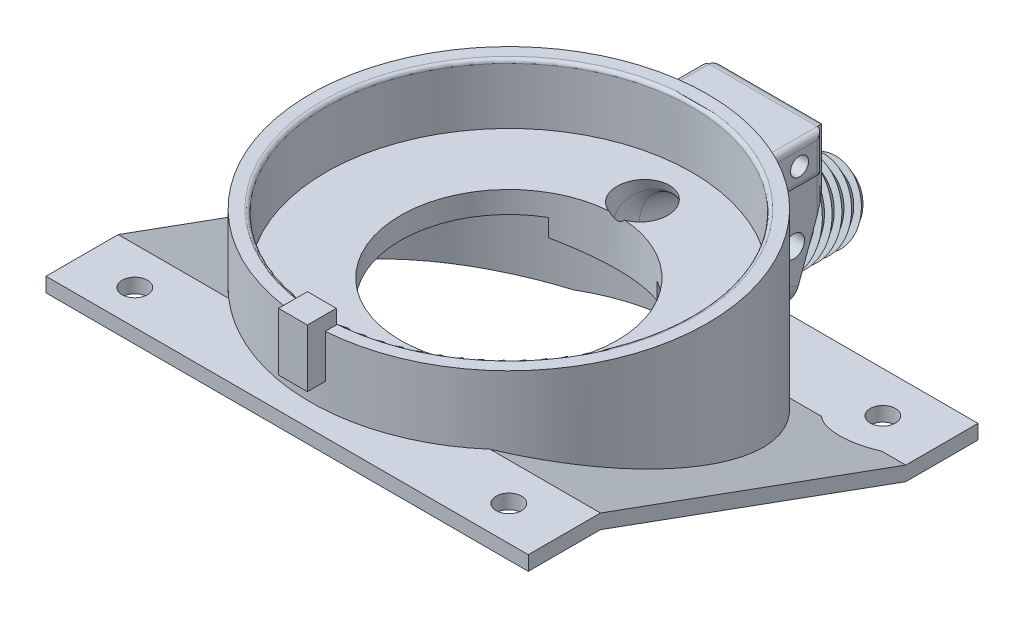
SolidWorks part; units mm, degrees
ref_plane "Front Plane" through (0, 0, 0) normal (0, 0, 1) x (1, 0, 0)
ref_plane "Top Plane" through (0, 0, 0) normal (0, 1, 0) x (1, 0, 0)
ref_plane "Right Plane" through (0, 0, 0) normal (1, 0, 0) x (0, 0, -1)
sketch "Sketch1" plane through (0, 0, 0) normal (0, 1, 0) x (1, 0, 0)
  line L0 (0, -33.8208) -> (0, 34.4324) construction
  line L1 (-28.4, 28.4) -> (28.4, 28.4)
  line L2 (-28.4, 28.4) -> (-28.4, -28.4)
  line L3 (-28.4, -28.4) -> (28.4, -28.4)
  line L4 (28.4, 28.4) -> (28.4, -28.4)
  line L5 (-28.4, 28.4) -> (28.4, -28.4) construction
  line L6 (-28.4, -28.4) -> (28.4, 28.4) construction
  line L7 (-31.5183, 0) -> (32.8915, 0) construction
  circle A0 centre (0, 0) radius 19.175
  point P0 (0, 0)
  dimension "D3" = 38.35
  dimension "D1" = 56.8
  dimension "D2" = 56.8
extrude "Boss-Extrude1" add sketch "Sketch1" along normal blind 5 contours L2 L3 L4 L1
extrude "Cut-Extrude1" cut sketch "Sketch1<4>" along normal blind 1.65 contours A0
sketch "Sketch1<4>" plane through (0, 0, 0) normal (0, 1, 0) x (1, 0, 0) same geometry as "Sketch1"
sketch "Sketch3" plane through (0, 5, 0) normal (0, 1, 0) x (1, 0, 0)
  circle A0 centre (0, 0) radius 15
  circle A1 centre (0, 0) radius 27.5
  dimension "D1" = 30
  dimension "D2" = 55
extrude "Cut-Extrude2" cut sketch "Sketch3" against normal up to surface (3.35 mm away) contours A0 up to face at (0, 1.65, 19.175)
extrude "Boss-Extrude2" add sketch "Sketch3<3>" along normal blind 25.04
sketch "Sketch3<3>" plane through (0, 5, 0) normal (0, 1, 0) x (1, 0, 0) same geometry as "Sketch3"
sketch "Sketch4" plane through (0, 30.04, 0) normal (0, 1, 0) x (1, 0, 0)
  circle A0 centre (0, 0) radius 27.5 construction
  circle A1 centre (0, 0) radius 27.5
  circle A2 centre (0, 0) radius 25.35
  dimension "D1" = 50.7
extrude "Boss-Extrude3" add sketch "Sketch4" along normal blind 8.3
sketch "Sketch14" plane through (0, 0, 28.4) normal (0, 0, 1) x (1, 0, 0)
  line L0 (27.5, 38.34) -> (-27.5, 38.34) construction
  line L1 (-2, 32.34) -> (2, 32.34)
  line L2 (-2, 32.34) -> (-2, 40.34)
  line L3 (-2, 40.34) -> (2, 40.34)
  line L4 (2, 32.34) -> (2, 40.34)
  line L5 (-2, 32.34) -> (2, 40.34) construction
  line L6 (-2, 40.34) -> (2, 32.34) construction
  line L8 (0, -5.1495) -> (0, 66.3845) construction
  point P0 (0, 36.34)
  dimension "D1" = 8
  dimension "D2" = 2
  dimension "D3" = 4
extrude "Boss-Extrude9" add sketch "Sketch14" against normal blind 2.5 and the other way blind 1.5
fillet "Fillet3" radius 0.5 1 edges at (0, 38.34, 25.35)
sketch "Sketch15" plane through (0, 0, 0) normal (1, 0, 0) x (0, 0, -1)
  line L0 (19.3563, 27.6919) -> (17.7409, 32.1304)
  line L1 (21.747, 25.3013) -> (58.7764, 11.8237)
  line L4 (27.5, 5) -> (27.5, 38.34) construction
  line L5 (25.35, 30.04) -> (-25.35, 30.04) construction
  arc A0 (19.3563, 27.6919) -> (21.747, 25.3013) centre (23.1151, 29.06) ccw
  dimension "D3" = 4
  dimension "D1" = 70
  dimension "D2" = 70
ref_plane "Plane2" through (0, 32.1304, -17.7409) normal (0, -0.9397, -0.342) x (-1, 0, 0)
sketch "Sketch16" plane through (0, 32.1304, -17.7409) normal (0, -0.9397, -0.342) x (-1, 0, 0)
  circle A0 centre (0, 0) radius 3.5
  dimension "D1" = 7
ref_axis "Axis2" through (0, 35.371, 5.9193) along (0, -0.342, -0.9397)
ref_plane "Plane5" through (0, -8.5427, -23.4709) normal (0, -0.342, -0.9397) x (1, 0, 0)
sketch "Sketch20" plane through (0, -8.5427, -23.4709) normal (0, -0.342, -0.9397) x (1, 0, 0)
  line L1 (-7.5, -38.7133) -> (7.5, -38.7133)
  line L2 (-7.5, -38.7133) -> (-7.5, -23.7133)
  line L3 (-7.5, -23.7133) -> (7.5, -23.7133)
  line L4 (7.5, -38.7133) -> (7.5, -23.7133)
  line L5 (-7.5, -38.7133) -> (7.5, -23.7133) construction
  line L6 (-7.5, -23.7133) -> (7.5, -38.7133) construction
  point P0 (0, -31.2133)
  dimension "D1" = 15
  dimension "D2" = 15
extrude "Boss-Extrude11" add sketch "Sketch20" against normal up to surface (10.9122 mm away) up to face at (0, 5, -27.5)
fillet "Fillet6" radius 3 1 edges at (-7.5, 14.673, -29.0194)
fillet "Fillet7" radius 3 1 edges at (7.5, 14.673, -29.0194)
sketch "Sketch22" plane through (0, -8.5427, -23.4709) normal (0, -0.342, -0.9397) x (1, 0, 0)
  line L0 (0, -31.2133) -> (-8.9055, -31.2133) construction
ref_plane "Plane6" through (0, 29.3309, -10.6756) normal (0, -0.9397, 0.342) x (-1, 0, 0)
sketch "Sketch26" plane through (0, 29.3309, -10.6756) normal (0, -0.9397, 0.342) x (-1, 0, 0)
  line L0 (0, 24.9772) -> (7.5, 24.9772)
  line L1 (0, 11.782) -> (0, 51.1878) construction
  line L3 (0, 24.9772) -> (8.9055, 24.9772) construction
  line L4 (0, 24.9772) -> (0, 50.9772)
  line L5 (7.5, 24.9772) -> (6, 26.9772)
  line L6 (6, 26.9772) -> (7, 26.9772)
  line L7 (7, 26.9772) -> (5.5, 28.9772)
  line L8 (5.5, 28.9772) -> (6.5, 28.9772)
  line L9 (6.5, 28.9772) -> (5, 30.9772)
  line L10 (5, 30.9772) -> (6, 30.9772)
  line L11 (6, 30.9772) -> (4.5, 32.9772)
  line L12 (4.5, 32.9772) -> (5.5, 32.9772)
  line L13 (5.5, 32.9772) -> (4, 34.9772)
  line L14 (4, 34.9772) -> (5, 34.9772)
  line L15 (5, 34.9772) -> (3.5, 36.9772)
  line L16 (3.5, 36.9772) -> (4.5, 36.9772)
  line L17 (4.5, 36.9772) -> (3, 38.9772)
  line L18 (3, 38.9772) -> (4, 38.9772)
  line L19 (4, 38.9772) -> (2.5, 40.9772)
  line L20 (2.5, 40.9772) -> (3.5, 40.9772)
  line L21 (3.5, 40.9772) -> (2, 42.9772)
  line L22 (2, 42.9772) -> (3, 42.9772)
  line L23 (3, 42.9772) -> (1.5, 44.9772)
  line L24 (1.5, 44.9772) -> (2.5, 44.9772)
  line L25 (2.5, 44.9772) -> (1, 46.9772)
  line L26 (1, 46.9772) -> (2, 46.9772)
  line L27 (2, 46.9772) -> (0.5, 48.9772)
  line L28 (0.5, 48.9772) -> (1.5, 48.9772)
  line L29 (1.5, 48.9772) -> (0, 50.9772)
  dimension "D1" = 7.5
  dimension "D2" = 2.5
  dimension "D3" = 1
  dimension "D4" = 2.5
  dimension "D5" = 0.5
  dimension "D6" = 2.5
  dimension "D7" = 1
  dimension "D8" = 2.5
  dimension "D9" = 1
  dimension "D10" = 0.5
  dimension "D11" = 2.5
  dimension "D12" = 1
  dimension "D13" = 2.5
  dimension "D14" = 1
  dimension "D15" = 2.5
  dimension "D16" = 1
  dimension "D17" = 2.5
  dimension "D18" = 1
  dimension "D19" = 1
  dimension "D20" = 2.5
  dimension "D21" = 1
  dimension "D22" = 0.5
  dimension "D23" = 1
  dimension "D24" = 0.5
  dimension "D25" = 2.5
  dimension "D26" = 1
  dimension "D27" = 2.5
revolve "Revolve4" add sketch "Sketch26" angle 360 about L1
sweep "Cut-Sweep3" cut profiles "Sketch16" path "Sketch15"
sketch "Sketch29" plane through (-7.5, 0, 0) normal (-1, 0, 0) x (0, 0, 1)
  line L0 (-50.9292, 14.6798) -> (29.578, 43.982) construction
  line L1 (-26.4575, 18.798) -> (-26.4575, 31.5681) construction
  line L2 (-31.9575, 34.9439) -> (-31.9575, 5.6751) construction
  circle A0 centre (-31.9575, 21.5849) radius 1.5
  circle A1 centre (-31.9575, 31.5849) radius 1.25
  dimension "D1" = 3
  dimension "D2" = 5.5
  dimension "D3" = 2.5
  dimension "D4" = 10
sketch "Sketch31" plane through (0, 38.34, 0) normal (0, 1, 0) x (1, 0, 0)
  line L0 (0, -5.9193) -> (0, 49.5105) construction
  line L1 (-7.5, 36.7116) -> (7.5, 36.7116)
  line L2 (-7.5, 36.7116) -> (-7.5, 25.6916)
  line L3 (-7.5, 25.6916) -> (7.5, 25.6916)
  line L4 (7.5, 36.7116) -> (7.5, 25.6916)
  line L5 (-7.5, 36.7116) -> (7.5, 25.6916) construction
  line L6 (-7.5, 25.6916) -> (7.5, 36.7116) construction
  line L7 (0, 36.7116) -> (7.5, 36.7116) construction
  line L8 (-7.5, 26.4575) -> (-7.5, 36.7116) construction
  point P0 (0, 31.2016)
  dimension "D1" = 0
  dimension "D2" = 0
extrude "Boss-Extrude12" add sketch "Sketch31" against normal up to surface (10.5041 mm away) up to face at (0, 29.2529, -32.8185)
sketch "Sketch33" plane through (0, 0, -36.7116) normal (0, 0, -1) x (-1, 0, 0)
  line L0 (7.5, 27.8359) -> (7.5, 38.34) construction
  line L1 (-7.5, 38.34) -> (7.5, 38.34)
  line L2 (-7.5, 38.34) -> (-7.5, 34.34)
  line L3 (-7.5, 34.34) -> (7.5, 34.34)
  line L4 (7.5, 38.34) -> (7.5, 34.34)
  dimension "D1" = 4
extrude "Cut-Extrude3" cut sketch "Sketch33" against normal up to surface (10.2541 mm away) up to face at (0, 5, -27.5)
extrude "Cut-Extrude4" cut sketch "Sketch29" against normal through all
fillet "Fillet8" radius 1.5 3 edges at (7.5, 31.088, -36.7116) (0, 34.34, -36.7116) (-7.5, 31.088, -36.7116)
ref_plane "Plane7" through (0, -12.9548, -35.5929) normal (0, 0.342, 0.9397) x (1, 0, 0)
sketch "Sketch35" plane through (0, -12.9548, -35.5929) normal (0, 0.342, 0.9397) x (1, 0, 0)
  line L1 (-9.025, 24.3636) -> (9.688, 24.3636)
  line L2 (-9.025, 24.3636) -> (-9.025, 36.9741)
  line L3 (-9.025, 36.9741) -> (9.688, 36.9741)
  line L4 (9.688, 24.3636) -> (9.688, 36.9741)
extrude "Cut-Extrude5" cut sketch "Sketch35" against normal blind 10
sketch "Sketch43" plane through (0, -12.9548, -35.5929) normal (0, 0.342, 0.9397) x (1, 0, 0)
  line L1 (10.1928, 24.0006) -> (-11.4613, 24.0006)
  line L2 (10.1928, 24.0006) -> (10.1928, 39.7537)
  line L3 (10.1928, 39.7537) -> (-11.4613, 39.7537)
  line L4 (-11.4613, 24.0006) -> (-11.4613, 39.7537)
extrude "Cut-Extrude6" cut sketch "Sketch43" along normal blind 1.4
sketch "Sketch44" plane through (0, 0, 0) normal (0, -1, 0) x (1, 0, 0)
  line L0 (-28.4, -28.4) -> (-28.4, 28.4) construction
  line L1 (28.4, -28.4) -> (-28.4, -28.4)
  line L2 (28.4, -28.4) -> (28.4, 28.4)
  line L3 (28.4, 28.4) -> (-28.4, 28.4)
  line L4 (-28.4, -28.4) -> (-28.4, 28.4)
  line L5 (-28.4, 28.4) -> (28.4, 28.4) construction
  line L6 (-28.4, -28.4) -> (28.4, -28.4) construction
extrude "Cut-Extrude8" cut sketch "Sketch44" against normal blind 13.5
sketch "Sketch48" plane through (0, 22.2832, -8.1104) normal (0, -0.9397, 0.342) x (1, 0, 0)
  line L1 (4.5, -20.2395) -> (-4.5, -20.2395)
  line L2 (4.5, -20.2395) -> (4.5, -24.9772)
  line L3 (4.5, -24.9772) -> (-4.5, -24.9772)
  line L4 (-4.5, -20.2395) -> (-4.5, -24.9772)
ref_plane "Plane3" through (-33.4, 0, 0) normal (1, 0, 0) x (0, 0, -1)
sketch "Sketch49" plane through (-33.4, 0, 0) normal (1, 0, 0) x (0, 0, -1)
  line L0 (-27.5, 13.5) -> (27.5, 13.5) construction
  line L1 (31.5813, 13.5) -> (21.5813, 13.5)
  line L2 (31.5813, 13.5) -> (31.5813, 11.5)
  line L3 (31.5813, 11.5) -> (21.5813, 11.5)
  line L4 (21.5813, 13.5) -> (-20.7049, 28.8909)
  line L5 (21.5813, 11.5) -> (-20.7049, 26.8909)
  line L9 (-20.7049, 28.8909) -> (-30.7049, 28.8909)
  line L11 (-20.7049, 26.8909) -> (-30.7049, 26.8909)
  line L12 (-30.7049, 28.8909) -> (-30.7049, 26.8909)
  dimension "D1" = 0
  dimension "D2" = 2
  dimension "D3" = 10
  dimension "D4" = 0
  dimension "D5" = 45
  dimension "D7" = 10
  dimension "D8" = 2
  dimension "D9" = 10
extrude "Boss-Extrude14" add sketch "Sketch49" along normal blind 66.8
extrude "Boss-Extrude15" add sketch "Sketch48" along normal up to surface (1.9804 mm away) up to face at (0, 13.5, -25.9011)
sketch "Sketch50" plane through (0, 17.0908, -6.2206) normal (0, -0.9397, 0.342) x (1, 0, 0)
  line L1 (-33.4, -16.3466) -> (33.4, -16.3466)
  line L2 (-33.4, -16.3466) -> (-33.4, 28.6534)
  line L3 (-33.4, 28.6534) -> (33.4, 28.6534)
  line L4 (33.4, -16.3466) -> (33.4, 28.6534)
extrude "Cut-Extrude9" cut sketch "Sketch50" along normal blind 66.8
sketch "Sketch51" plane through (0, 26.8909, 0) normal (0, -1, 0) x (1, 0, 0)
  line L1 (-33.4, 20.7049) -> (33.4, 20.7049)
  line L2 (-33.4, 20.7049) -> (-33.4, 30.7049)
  line L3 (-33.4, 30.7049) -> (33.4, 30.7049)
  line L4 (33.4, 20.7049) -> (33.4, 30.7049)
extrude "Cut-Extrude10" cut sketch "Sketch51" along normal blind 66.8
sketch "Sketch52" plane through (0, 30.04, 0) normal (0, 1, 0) x (1, 0, 0)
  circle A0 centre (0, 0) radius 15
extrude "Cut-Extrude11" cut sketch "Sketch52" against normal blind 66.8
sketch "Sketch53" plane through (0, 11.5, 0) normal (0, -1, 0) x (1, 0, 0)
  line L0 (-7.5, -23.8485) -> (-7.5, -7.844)
  line L1 (-7.5, -7.844) -> (7.5, -7.844)
  line L2 (7.5, -7.844) -> (7.5, -23.8485)
  line L3 (-7.5, -32.6074) -> (-7.5, -26.4575) construction
  line L4 (7.5, -26.4575) -> (7.5, -32.6074) construction
  arc A0 (7.5, -23.8485) -> (-7.5, -23.8485) centre (0, 0) ccw
  dimension "D1" = 50
  dimension "D2" = 0
  dimension "D3" = 0
extrude "Cut-Extrude12" cut sketch "Sketch53" against normal offset from surface (15.54 mm away) 3 up to face at (0, 30.04, -3.6132)
sketch "Sketch54" plane through (0, 0, 0) normal (0, 1, 0) x (1, 0, 0)
  circle A0 centre (25.9, 25.9) radius 1.75
  circle A1 centre (25.9, -25.9) radius 1.75
  circle A2 centre (-25.9, -25.9) radius 1.75
  circle A3 centre (-25.9, 25.9) radius 1.75
  point P0 (0, 0)
  dimension "D3" = 3.5
  dimension "D4" = 3.5
  dimension "D1" = 3.5
  dimension "D2" = 3.5
extrude "Cut-Extrude13" cut sketch "Sketch54" against normal through all both and the other way through all
sketch "Sketch55" plane through (0, 13.5, 0) normal (0, 1, 0) x (1, 0, 0)
  circle A0 centre (25.9, 25.9) radius 6
  circle A1 centre (-25.9, 25.9) radius 6
  dimension "D1" = 12
  dimension "D2" = 12
extrude "Cut-Extrude14" cut sketch "Sketch55" along normal blind 10
sketch "Sketch56" plane through (-7.5, 0, 0) normal (-1, 0, 0) x (0, 0, 1)
  line L1 (-31.9575, 31.5849) -> (-31.9575, 35.2583) construction
  line L2 (-35.2116, 34.34) -> (-26.4575, 34.34)
  line L3 (-35.2116, 34.34) -> (-35.2116, 28.8349)
  line L4 (-35.2116, 28.8349) -> (-26.4575, 28.8349)
  line L5 (-26.4575, 34.34) -> (-26.4575, 28.8349)
  line L6 (-31.9575, 31.5849) -> (-31.9575, 28.3602) construction
  line L7 (-31.9575, 31.5849) -> (-37.5104, 31.5849) construction
  line L8 (-31.9575, 31.5849) -> (-27.565, 31.5849) construction
  line L9 (-35.2116, 34.34) -> (-35.2116, 23.7147) construction
  line L10 (-26.4575, 18.798) -> (-26.4575, 34.34) construction
  line L11 (-26.4575, 34.34) -> (-35.2116, 34.34) construction
  circle A0 centre (-31.9575, 31.5849) radius 1.25 construction
  dimension "D1" = 2.75
extrude "Boss-Extrude16" add sketch "Sketch56" along normal blind 0.8
sketch "Sketch57" plane through (7.5, 0, 0) normal (1, 0, 0) x (0, 0, -1)
  line L0 (26.4575, 34.34) -> (35.2116, 34.34) construction
  line L1 (26.4575, 34.34) -> (35.2116, 34.34)
  line L2 (26.4575, 34.34) -> (26.4575, 28.8349)
  line L3 (26.4575, 28.8349) -> (35.2116, 28.8349)
  line L4 (35.2116, 34.34) -> (35.2116, 28.8349)
  line L5 (26.4575, 34.34) -> (26.4575, 18.798) construction
  line L6 (35.2116, 23.7147) -> (35.2116, 34.34) construction
  circle A0 centre (31.9575, 31.5849) radius 1.25 construction
  dimension "D1" = 2.75
extrude "Boss-Extrude17" add sketch "Sketch57" along normal blind 0.8
sketch "Sketch58" plane through (8.3, 0, 0) normal (1, 0, 0) x (0, 0, -1)
  circle A0 centre (31.9575, 31.5849) radius 1.25
  dimension "D1" = 2.5
extrude "Cut-Extrude15" cut sketch "Sketch58" against normal through all both and the other way through all
fillet "Fillet10" radius 0.8 6 edges at (8.3, 28.8349, -30.8346) (8.3, 31.5875, -35.2116) (8.3, 34.34, -30.8346) (-8.3, 28.8349, -30.8346) (-8.3, 31.5875, -35.2116) (-8.3, 34.34, -30.8346)
sketch "Sketch59" plane through (0, 11.5, 0) normal (0, -1, 0) x (-1, 0, 0)
  circle A0 centre (0, 0) radius 25
  arc A1 (-7.5, 23.8485) -> (7.5, 23.8485) centre (0, 0) ccw construction
  dimension "D1" = 0
extrude "Cut-Extrude16" cut sketch "Sketch59" against normal blind 7.5
ref_plane "Plane8" through (6, 32.84, -36.7116) normal (1, 0, 0) x (0, 0, -1)
sketch "Sketch61" plane through (-7.5, 0, 0) normal (-1, 0, 0) x (0, 0, 1)
  line L0 (-23.8485, 19) -> (-12.9904, 24.5939)
  line L1 (-12.9904, 27.04) -> (-12.9904, 19) construction
  line L2 (-12.9904, 24.5939) -> (-12.9904, 19)
  line L3 (-12.9904, 19) -> (-23.8485, 19)
extrude "Cut-Extrude17" cut sketch "Sketch61" against normal up to surface (15 mm away) up to face at (7.5, 23.02, -18.4194)
ref_plane "Plane9" through (4, 0, 0) normal (1, 0, 0) x (0, 0, -1)
sketch "Sketch64" plane through (4, 0, 0) normal (1, 0, 0) x (0, 0, -1)
  circle A0 centre (31.9575, 21.5849) radius 1.5
  circle A1 centre (31.9575, 21.5849) radius 0.55
  dimension "D1" = 3
  dimension "D2" = 1.1
ref_plane "Plane10" through (-4, 0, 0) normal (1, 0, 0) x (0, 0, -1)
extrude "Boss-Extrude18" add sketch "Sketch64" against normal up to surface (0.5378 mm away) up to face at (0, 13.5661, -43.7558)
sketch "Sketch65" plane through (-4, 0, 0) normal (1, 0, 0) x (0, 0, -1)
  circle A0 centre (31.9575, 21.5849) radius 1.5
  circle A1 centre (31.9575, 21.5849) radius 1.5 construction
  circle A2 centre (31.9575, 21.5849) radius 0.55
  circle A3 centre (31.9575, 21.5849) radius 0.55 construction
extrude "Boss-Extrude19" add sketch "Sketch65" along normal up to surface (7.4622 mm away)
sketch "Sketch67" plane through (0, -12.4759, -34.2773) normal (0, -0.342, -0.9397) x (-1, 0, 0)
  circle A0 centre (0, 31.2133) radius 3.5
extrude "Cut-Extrude18" cut sketch "Sketch67" against normal blind 20
